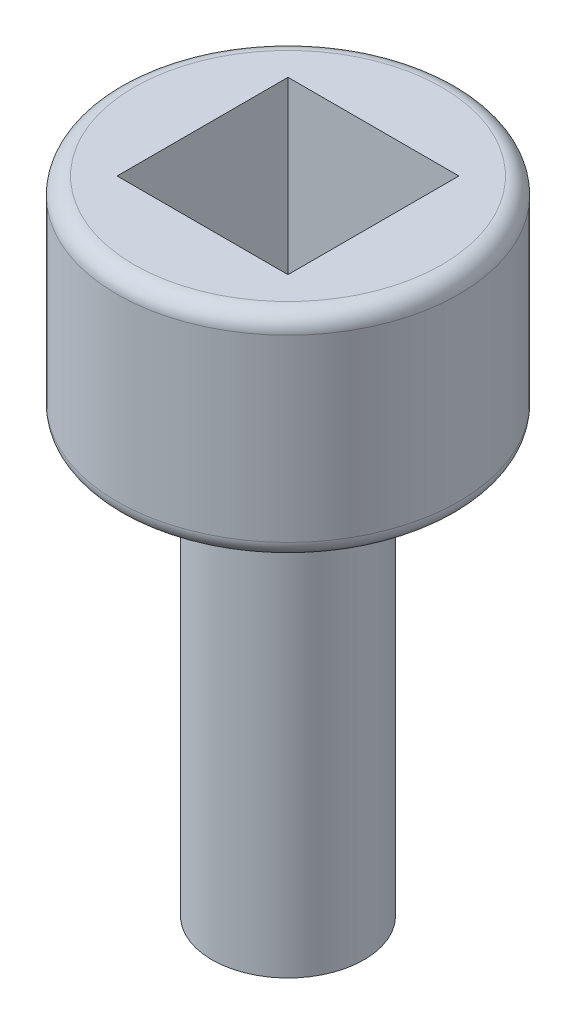
SolidWorks part; units mm, degrees
ref_plane "Front Plane" through (0, 0, 0) normal (0, 0, 1) x (1, 0, 0)
ref_plane "Top Plane" through (0, 0, 0) normal (0, 1, 0) x (1, 0, 0)
ref_plane "Right Plane" through (0, 0, 0) normal (1, 0, 0) x (0, 0, -1)
sketch "Sketch1" plane through (0, 0, 0) normal (0, 1, 0) x (1, 0, 0)
  circle A0 centre (0, 0) radius 2.54
  dimension "D1" = 5.08
extrude "Boss-Extrude1" add sketch "Sketch1" against normal blind 3.175 contours A0
sketch "Sketch2" plane through (0, 0, 0) normal (0, 1, 0) x (1, 0, 0)
  circle A0 centre (0, 0) radius 1.1303
  dimension "D1" = 2.2606
extrude "Boss-Extrude2" add sketch "Sketch2" against normal blind 9.525
sketch "Sketch3" plane through (0, 0, 0) normal (0, 1, 0) x (1, 0, 0)
  line L1 (-1.27, 1.27) -> (1.27, 1.27)
  line L2 (-1.27, 1.27) -> (-1.27, -1.27)
  line L3 (-1.27, -1.27) -> (1.27, -1.27)
  line L4 (1.27, 1.27) -> (1.27, -1.27)
  dimension "D1" = 2.54
  dimension "D2" = 2.54
  dimension "D3" = 1.27
  dimension "D4" = 1.27
extrude "Cut-Extrude1" cut sketch "Sketch3" against normal blind 2.54
fillet "Fillet3" radius 0.254 2 edges at (0, 0, 2.54) (0, -3.175, 2.54)
